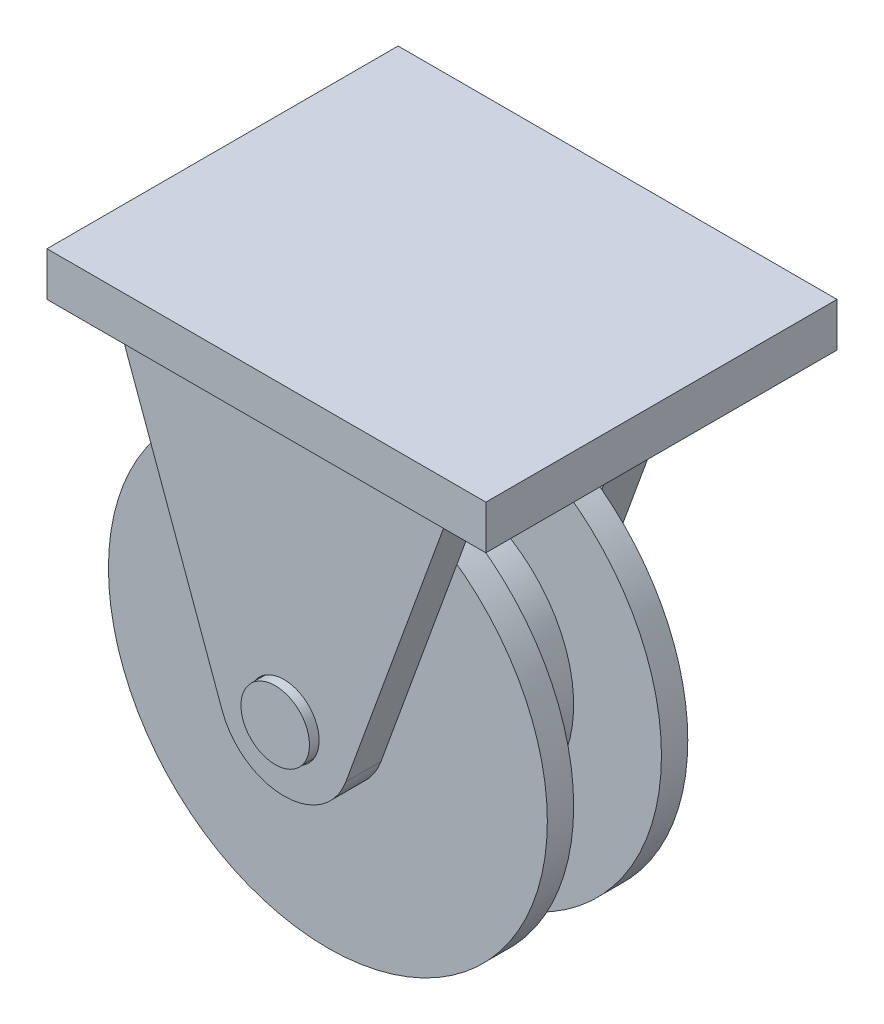
SolidWorks part; units mm, degrees
ref_plane "前视基准面" through (0, 0, 0) normal (0, 0, 1) x (1, 0, 0)
ref_plane "上视基准面" through (0, 0, 0) normal (0, 1, 0) x (1, 0, 0)
ref_plane "右视基准面" through (0, 0, 0) normal (1, 0, 0) x (0, 0, -1)
sketch "草图1" plane through (0, 0, 0) normal (0, 0, 1) x (1, 0, 0)
  circle A0 centre (0, 0) radius 25
  dimension "D1" = 50
extrude "凸台-拉伸1" add sketch "草图1" along normal blind 3
sketch "草图2" plane through (0, 0, 3) normal (0, 0, 1) x (1, 0, 0)
  line L0 (-18.9004, 30) -> (-7.0477, -2.5652)
  line L1 (18.9004, 30) -> (7.0477, -2.5652)
  line L2 (-18.9004, 30) -> (18.9004, 30)
  line L3 (0, 0) -> (0, 66.6841) construction
  circle A0 centre (0, 0) radius 4
  arc A1 (-7.0477, -2.5652) -> (7.0477, -2.5652) centre (0, 0) ccw
  dimension "D1" = 8
  dimension "D2" = 15
  dimension "D3" = 30
  dimension "D4" = 20
extrude "凸台-拉伸2" add sketch "草图2" along normal blind 5 contours A0 | L0 A1 L1 L2
sketch "草图3" plane through (0, 0, 3) normal (0, 0, 1) x (1, 0, 0)
  circle A2 centre (0, 0) radius 3.9
  dimension "D1" = 7.8
extrude "凸台-拉伸4" add sketch "草图3" along normal blind 6
sketch "草图5" plane through (0, 0, 0) normal (0, 0, -1) x (-1, 0, 0)
  circle A0 centre (0, 0) radius 15
  dimension "D1" = 30
extrude "凸台-拉伸5" add sketch "草图5" along normal blind 10
ref_plane "基准面2" through (0, 0, -5) normal (0, 0, 1) x (1, 0, 0)
mirror "镜向1" about plane through (0, 0, -5) normal (0, 0, 1) of "凸台-拉伸1", "凸台-拉伸2"
sketch "草图6" plane through (0, 0, -13) normal (0, 0, -1) x (-1, 0, 0)
  circle A2 centre (0, 0) radius 3.9
  dimension "D1" = 7.8
extrude "凸台-拉伸6" add sketch "草图6" along normal blind 6
sketch "草图8" plane through (0, 30, 0) normal (0, 1, 0) x (1, 0, 0)
  line L0 (0, 0) -> (0, 67.0188) construction
  line L1 (-25, -10) -> (25, -10)
  line L2 (-25, -10) -> (-25, 30)
  line L3 (-25, 30) -> (25, 30)
  line L4 (25, -10) -> (25, 30)
  line L5 (0, 0) -> (69.1147, 0) construction
  point P0 (0, 0)
  dimension "D1" = 50
  dimension "D2" = 40
  dimension "D3" = 10
extrude "凸台-拉伸7" add sketch "草图8" along normal blind 5
extrude "切除-拉伸1" cut sketch "草图2<3>" along normal blind 1
sketch "草图2<3>" plane through (0, 0, 3) normal (0, 0, 1) x (1, 0, 0) same geometry as "草图2"
